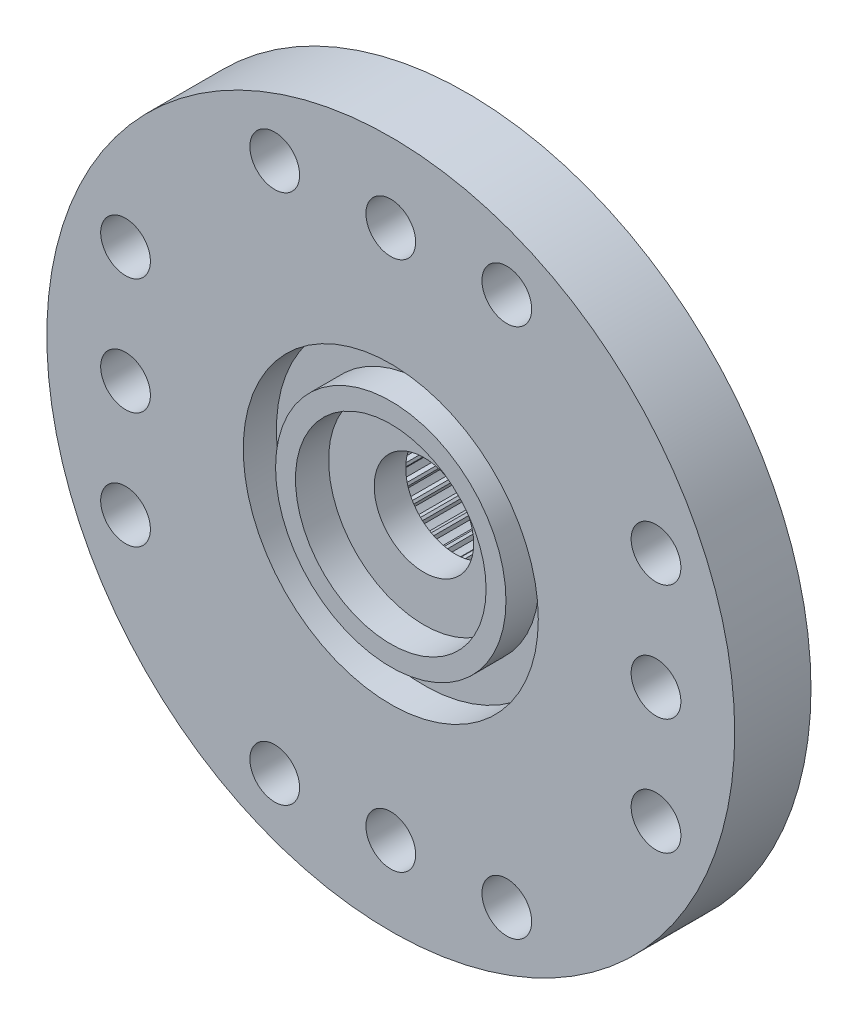
SolidWorks part; units mm, degrees
ref_plane "Plan de face" through (0, 0, 0) normal (0, 0, 1) x (1, 0, 0)
ref_plane "Plan de dessus" through (0, 0, 0) normal (0, 1, 0) x (1, 0, 0)
ref_plane "Plan de droite" through (0, 0, 0) normal (1, 0, 0) x (0, 0, -1)
sketch "Esquisse1" plane through (0, 0, 0) normal (0, 0, 1) x (1, 0, 0)
  circle A10 centre (0, 0) radius 10.375
  dimension "D7" = 20.75
extrude "Boss.-Extru.1" add sketch "Esquisse1" along normal blind 2.3
sketch "Esquisse2" plane through (0, 0, 2.3) normal (0, 0, 1) x (1, 0, 0)
  circle A0 centre (0, 0) radius 4.45
  dimension "D1" = 8.9
extrude "Enlèv. mat.-Extru.1" cut sketch "Esquisse2" against normal blind 1
sketch "Esquisse3" plane through (0, 0, 1.3) normal (0, 0, 1) x (1, 0, 0)
  circle A0 centre (0, 0) radius 2.875
  circle A1 centre (0, 0) radius 3.475
  dimension "D1" = 5.75
  dimension "D2" = 0.6
extrude "Boss.-Extru.2" add sketch "Esquisse3" along normal up to surface (1 mm away) up to face at (4.45, 0, 2.3)
sketch "Esquisse4" plane through (0, 0, 0) normal (0, 0, -1) x (-1, 0, 0)
  circle A0 centre (0, 0) radius 4.4
  dimension "D1" = 8.8
extrude "Boss.-Extru.3" add sketch "Esquisse4" along normal blind 3
sketch "Esquisse5" plane through (0, 0, 1.3) normal (0, 0, 1) x (1, 0, 0)
  circle A0 centre (0, 0) radius 1.5
  dimension "D1" = 3
extrude "Enlèv. mat.-Extru.2" cut sketch "Esquisse5" against normal through all
sketch "Esquisse6" plane through (0, 0, -3) normal (0, 0, -1) x (-1, 0, 0)
  line L0 (-0.1143, 2.9978) -> (-0.0406, 2.8652)
  line L1 (0.0406, 2.8652) -> (0.1143, 2.9978)
  line L2 (0, 2.8652) -> (0, 0) construction
  line L3 (-0.0406, 2.8652) -> (0.0406, 2.8652)
  line L4 (0.439, 2.8316) -> (0.5304, 2.9527)
  line L5 (0.3041, 2.9846) -> (0.3585, 2.8429)
  line L6 (0.3585, 2.8429) -> (0.439, 2.8316)
  line L7 (0.8288, 2.743) -> (0.9362, 2.8502)
  line L8 (0.7165, 2.9132) -> (0.7507, 2.7654)
  line L9 (0.7507, 2.7654) -> (0.8288, 2.743)
  line L10 (1.2025, 2.6009) -> (1.3237, 2.6922)
  line L11 (1.1149, 2.7851) -> (1.1283, 2.634)
  line L12 (1.1283, 2.634) -> (1.2025, 2.6009)
  line L13 (1.5527, 2.4083) -> (1.6855, 2.4817)
  line L14 (1.4917, 2.6029) -> (1.4839, 2.4513)
  line L15 (1.4839, 2.4513) -> (1.5527, 2.4083)
  line L16 (1.8728, 2.1687) -> (2.0145, 2.223)
  line L17 (1.8394, 2.3699) -> (1.8106, 2.2209)
  line L18 (1.8106, 2.2209) -> (1.8728, 2.1687)
  line L19 (2.1564, 1.887) -> (2.3043, 1.921)
  line L20 (2.1514, 2.0909) -> (2.1021, 1.9473)
  line L21 (2.1021, 1.9473) -> (2.1564, 1.887)
  line L22 (2.398, 1.5685) -> (2.5492, 1.5816)
  line L23 (2.4214, 1.7711) -> (2.3526, 1.6358)
  line L24 (2.3526, 1.6358) -> (2.398, 1.5685)
  line L25 (2.593, 1.2195) -> (2.7445, 1.2114)
  line L26 (2.6443, 1.4169) -> (2.5574, 1.2925)
  line L27 (2.5574, 1.2925) -> (2.593, 1.2195)
  line L28 (2.7375, 0.8468) -> (2.8864, 0.8177)
  line L29 (2.8158, 1.0351) -> (2.7124, 0.924)
  line L30 (2.7124, 0.924) -> (2.7375, 0.8468)
  line L31 (2.8287, 0.4575) -> (2.9721, 0.408)
  line L32 (2.9324, 0.6331) -> (2.8146, 0.5375)
  line L33 (2.8146, 0.5375) -> (2.8287, 0.4575)
  line L34 (2.8648, 0.0594) -> (3, -0.0096)
  line L35 (2.992, 0.2188) -> (2.862, 0.1406)
  line L36 (2.862, 0.1406) -> (2.8648, 0.0594)
  line L37 (2.8452, -0.3399) -> (2.9695, -0.427)
  line L38 (2.9933, -0.1997) -> (2.8537, -0.2591)
  line L39 (2.8537, -0.2591) -> (2.8452, -0.3399)
  line L40 (2.7702, -0.7325) -> (2.8811, -0.8361)
  line L41 (2.9364, -0.6144) -> (2.7899, -0.6537)
  line L42 (2.7899, -0.6537) -> (2.7702, -0.7325)
  line L43 (2.6413, -1.111) -> (2.7367, -1.229)
  line L44 (2.8223, -1.017) -> (2.6717, -1.0357)
  line L45 (2.6717, -1.0357) -> (2.6413, -1.111)
  line L46 (2.461, -1.4677) -> (2.5391, -1.5979)
  line L47 (2.6533, -1.3999) -> (2.5016, -1.3974)
  line L48 (2.5016, -1.3974) -> (2.461, -1.4677)
  line L49 (2.2328, -1.796) -> (2.292, -1.9357)
  line L50 (2.4327, -1.7556) -> (2.2828, -1.732)
  line L51 (2.2828, -1.732) -> (2.2328, -1.796)
  line L52 (1.9611, -2.0892) -> (2.0003, -2.2358)
  line L53 (2.1647, -2.0771) -> (2.0195, -2.0328)
  line L54 (2.0195, -2.0328) -> (1.9611, -2.0892)
  line L55 (1.6512, -2.3418) -> (1.6696, -2.4925)
  line L56 (1.8545, -2.3581) -> (1.7169, -2.2941)
  line L57 (1.7169, -2.2941) -> (1.6512, -2.3418)
  line L58 (1.3093, -2.5488) -> (1.3065, -2.7006)
  line L59 (1.5083, -2.5933) -> (1.381, -2.5107)
  line L60 (1.381, -2.5107) -> (1.3093, -2.5488)
  line L61 (0.9418, -2.7063) -> (0.9179, -2.8561)
  line L62 (1.1327, -2.7779) -> (1.0181, -2.6785)
  line L63 (1.0181, -2.6785) -> (0.9418, -2.7063)
  line L64 (0.556, -2.811) -> (0.5115, -2.9561)
  line L65 (0.7351, -2.9086) -> (0.6354, -2.7941)
  line L66 (0.6354, -2.7941) -> (0.556, -2.811)
  line L67 (0.1594, -2.861) -> (0.0951, -2.9985)
  line L68 (0.3231, -2.9825) -> (0.2404, -2.8553)
  line L69 (0.2404, -2.8553) -> (0.1594, -2.861)
  line L70 (-0.2404, -2.8553) -> (-0.3231, -2.9825)
  line L71 (-0.0951, -2.9985) -> (-0.1594, -2.861)
  line L72 (-0.1594, -2.861) -> (-0.2404, -2.8553)
  line L73 (-0.6354, -2.7941) -> (-0.7351, -2.9086)
  line L74 (-0.5115, -2.9561) -> (-0.556, -2.811)
  line L75 (-0.556, -2.811) -> (-0.6354, -2.7941)
  line L76 (-1.0181, -2.6785) -> (-1.1327, -2.7779)
  line L77 (-0.9179, -2.8561) -> (-0.9418, -2.7063)
  line L78 (-0.9418, -2.7063) -> (-1.0181, -2.6785)
  line L79 (-1.381, -2.5107) -> (-1.5083, -2.5933)
  line L80 (-1.3065, -2.7006) -> (-1.3093, -2.5488)
  line L81 (-1.3093, -2.5488) -> (-1.381, -2.5107)
  line L82 (-1.7169, -2.2941) -> (-1.8545, -2.3581)
  line L83 (-1.6696, -2.4925) -> (-1.6512, -2.3418)
  line L84 (-1.6512, -2.3418) -> (-1.7169, -2.2941)
  line L85 (-2.0195, -2.0328) -> (-2.1647, -2.0771)
  line L86 (-2.0003, -2.2358) -> (-1.9611, -2.0892)
  line L87 (-1.9611, -2.0892) -> (-2.0195, -2.0328)
  line L88 (-2.2828, -1.732) -> (-2.4327, -1.7556)
  line L89 (-2.292, -1.9357) -> (-2.2328, -1.796)
  line L90 (-2.2328, -1.796) -> (-2.2828, -1.732)
  line L91 (-2.5016, -1.3974) -> (-2.6533, -1.3999)
  line L92 (-2.5391, -1.5979) -> (-2.461, -1.4677)
  line L93 (-2.461, -1.4677) -> (-2.5016, -1.3974)
  line L94 (-2.6717, -1.0357) -> (-2.8223, -1.017)
  line L95 (-2.7367, -1.229) -> (-2.6413, -1.111)
  line L96 (-2.6413, -1.111) -> (-2.6717, -1.0357)
  line L97 (-2.7899, -0.6537) -> (-2.9364, -0.6144)
  line L98 (-2.8811, -0.8361) -> (-2.7702, -0.7325)
  line L99 (-2.7702, -0.7325) -> (-2.7899, -0.6537)
  line L100 (-2.8537, -0.2591) -> (-2.9933, -0.1997)
  line L101 (-2.9695, -0.427) -> (-2.8452, -0.3399)
  line L102 (-2.8452, -0.3399) -> (-2.8537, -0.2591)
  line L103 (-2.862, 0.1406) -> (-2.992, 0.2188)
  line L104 (-3, -0.0096) -> (-2.8648, 0.0594)
  line L105 (-2.8648, 0.0594) -> (-2.862, 0.1406)
  line L106 (-2.8146, 0.5375) -> (-2.9324, 0.6331)
  line L107 (-2.9721, 0.408) -> (-2.8287, 0.4575)
  line L108 (-2.8287, 0.4575) -> (-2.8146, 0.5375)
  line L109 (-2.7124, 0.924) -> (-2.8158, 1.0351)
  line L110 (-2.8864, 0.8177) -> (-2.7375, 0.8468)
  line L111 (-2.7375, 0.8468) -> (-2.7124, 0.924)
  line L112 (-2.5574, 1.2925) -> (-2.6443, 1.4169)
  line L113 (-2.7445, 1.2114) -> (-2.593, 1.2195)
  line L114 (-2.593, 1.2195) -> (-2.5574, 1.2925)
  line L115 (-2.3526, 1.6358) -> (-2.4214, 1.7711)
  line L116 (-2.5492, 1.5816) -> (-2.398, 1.5685)
  line L117 (-2.398, 1.5685) -> (-2.3526, 1.6358)
  line L118 (-2.1021, 1.9473) -> (-2.1514, 2.0909)
  line L119 (-2.3043, 1.921) -> (-2.1564, 1.887)
  line L120 (-2.1564, 1.887) -> (-2.1021, 1.9473)
  line L121 (-1.8106, 2.2209) -> (-1.8394, 2.3699)
  line L122 (-2.0145, 2.223) -> (-1.8728, 2.1687)
  line L123 (-1.8728, 2.1687) -> (-1.8106, 2.2209)
  line L124 (-1.4839, 2.4513) -> (-1.4917, 2.6029)
  line L125 (-1.6855, 2.4817) -> (-1.5527, 2.4083)
  line L126 (-1.5527, 2.4083) -> (-1.4839, 2.4513)
  line L127 (-1.1283, 2.634) -> (-1.1149, 2.7851)
  line L128 (-1.3237, 2.6922) -> (-1.2025, 2.6009)
  line L129 (-1.2025, 2.6009) -> (-1.1283, 2.634)
  line L130 (-0.7507, 2.7654) -> (-0.7165, 2.9132)
  line L131 (-0.9362, 2.8502) -> (-0.8288, 2.743)
  line L132 (-0.8288, 2.743) -> (-0.7507, 2.7654)
  line L133 (-0.3585, 2.8429) -> (-0.3041, 2.9846)
  line L134 (-0.5304, 2.9527) -> (-0.439, 2.8316)
  line L135 (-0.439, 2.8316) -> (-0.3585, 2.8429)
  circle A0 centre (0, 0) radius 3
  point P187 (0, 0)
  circle M5 centre (0, 0) radius 1.5
  dimension "D1" = 6
  dimension "D2" = 45
extrude "Enlèv. mat.-Extru.3" cut sketch "Esquisse6" against normal blind 3.35 contours L35 A0 L31 L33 L32 L28 L30 L29 L25 L27 L26 L22 L24 L23 L19 L21 L20 L16 L18 L17 L13 L15 L14 L10 L12 L11 L7 L9 L8 L4 L6 L5 L1 L3 L0 L133 M5 region at (0.1516, 2.8903, -3)
sketch "Esquisse7" plane through (0, 0, 2.3) normal (0, 0, 1) x (1, 0, 0)
  line L1 (0, 0) -> (0, 8) construction
  circle A9 centre (-8, 0) radius 0.75
  circle A26 centre (0, 0) radius 8 construction
  circle A28 centre (-8, 3.5) radius 0.75
  circle A29 centre (-8, -3.5) radius 0.75
  circle A30 centre (0, 8) radius 0.75
  circle A31 centre (3.5, 8) radius 0.75
  circle A32 centre (-3.5, 8) radius 0.75
  circle A33 centre (8, 0) radius 0.75
  circle A34 centre (8, -3.5) radius 0.75
  circle A35 centre (8, 3.5) radius 0.75
  circle A36 centre (0, -8) radius 0.75
  circle A37 centre (-3.5, -8) radius 0.75
  circle A38 centre (3.5, -8) radius 0.75
  point P28 (0, 0)
  dimension "D1" = 1.5
  dimension "D2" = 8
  dimension "D6" = 16
  dimension "D3" = 4
  dimension "D4" = 2
  dimension "D5" = 2
  dimension "D7" = 3.5
  dimension "D8" = 3.5
extrude "Enlèv. mat.-Extru.4" cut sketch "Esquisse7" against normal blind 3.35
